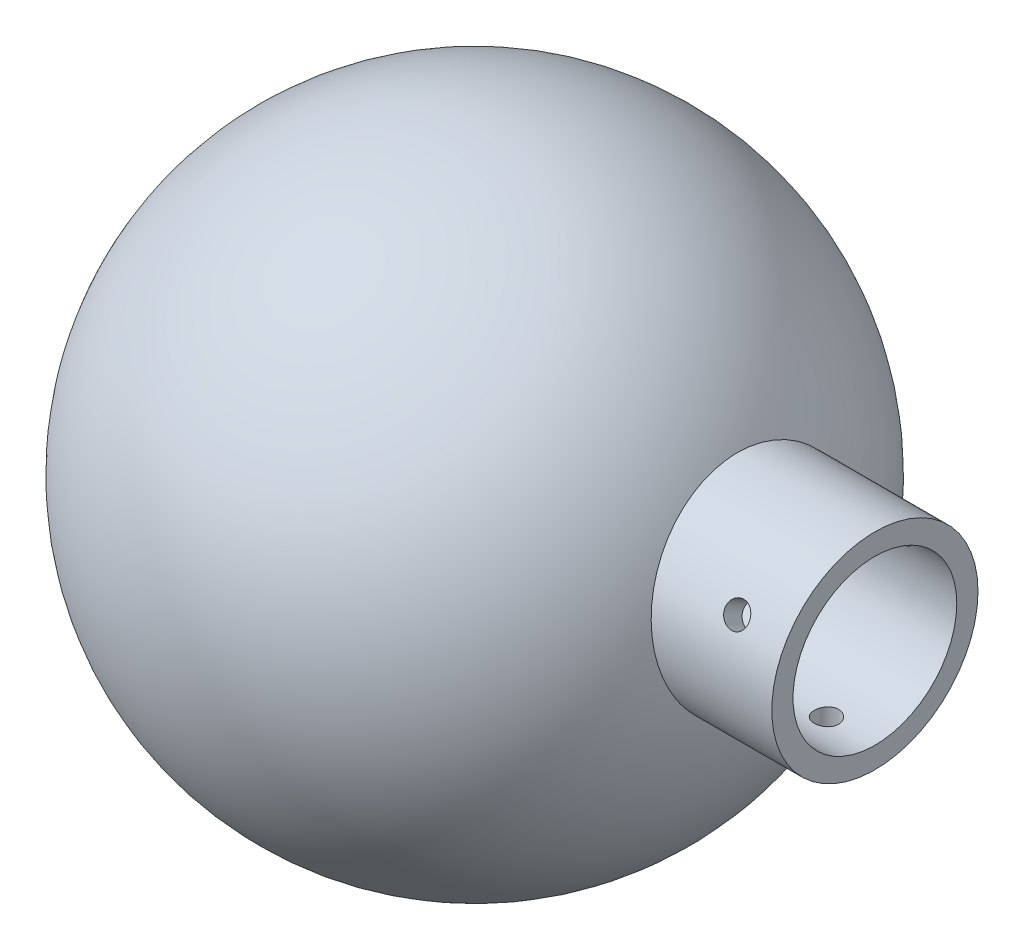
SolidWorks part; units mm, degrees
ref_plane "Front Plane" through (0, 0, 0) normal (0, 0, 1) x (1, 0, 0)
ref_plane "Top Plane" through (0, 0, 0) normal (0, 1, 0) x (1, 0, 0)
ref_plane "Right Plane" through (0, 0, 0) normal (1, 0, 0) x (0, 0, -1)
sketch "Sketch1" plane through (0, 0, 0) normal (0, 0, 1) x (1, 0, 0)
  line L0 (-63.5, 0) -> (-60.96, 0)
  line L1 (60.96, 0) -> (63.5, 0)
  arc A0 (63.5, 0) -> (-63.5, 0) centre (0, 0) ccw
  arc A1 (60.96, 0) -> (-60.96, 0) centre (0, 0) ccw
  dimension "D1" = 63.5
  dimension "D2" = 60.96
revolve "Revolve1" add sketch "Sketch1" angle 360 about L0
sketch "Sketch2" plane through (0, 0, 0) normal (1, 0, 0) x (0, 0, -1)
  line L0 (0, 69.85) -> (0, -69.85) construction
  line L1 (69.85, 0) -> (-69.85, 0) construction
  circle A0 centre (0, 10.0076) radius 21.59
  circle A1 centre (0, 10.0076) radius 17.145
  dimension "D1" = 10.0076
  dimension "D2" = 34.29
  dimension "D3" = 43.18
extrude "Boss-Extrude1" add sketch "Sketch2" along normal blind 83.82 and the other way up to next
extrude "Cut-Extrude3" cut sketch "Sketch2<4>" along normal blind 138.938 contours A1
sketch "Sketch2<4>" plane through (0, 0, 0) normal (1, 0, 0) x (0, 0, -1) same geometry as "Sketch2"
sketch "Sketch4" plane through (0, 0, 0) normal (0, 1, 0) x (1, 0, 0)
  line L0 (-69.85, 0) -> (69.85, 0) construction
  line L1 (83.82, -21.59) -> (83.82, 21.59) construction
  circle A0 centre (73.66, 0) radius 2.54
  dimension "D1" = 10.16
extrude "Cut-Extrude4" cut sketch "Sketch4" against normal blind 138.938
pattern_circular "CirPattern1" count 3 every 120 about axis through (-63.502, 10.0076, 0) along (1, 0, 0) of "Cut-Extrude4"
